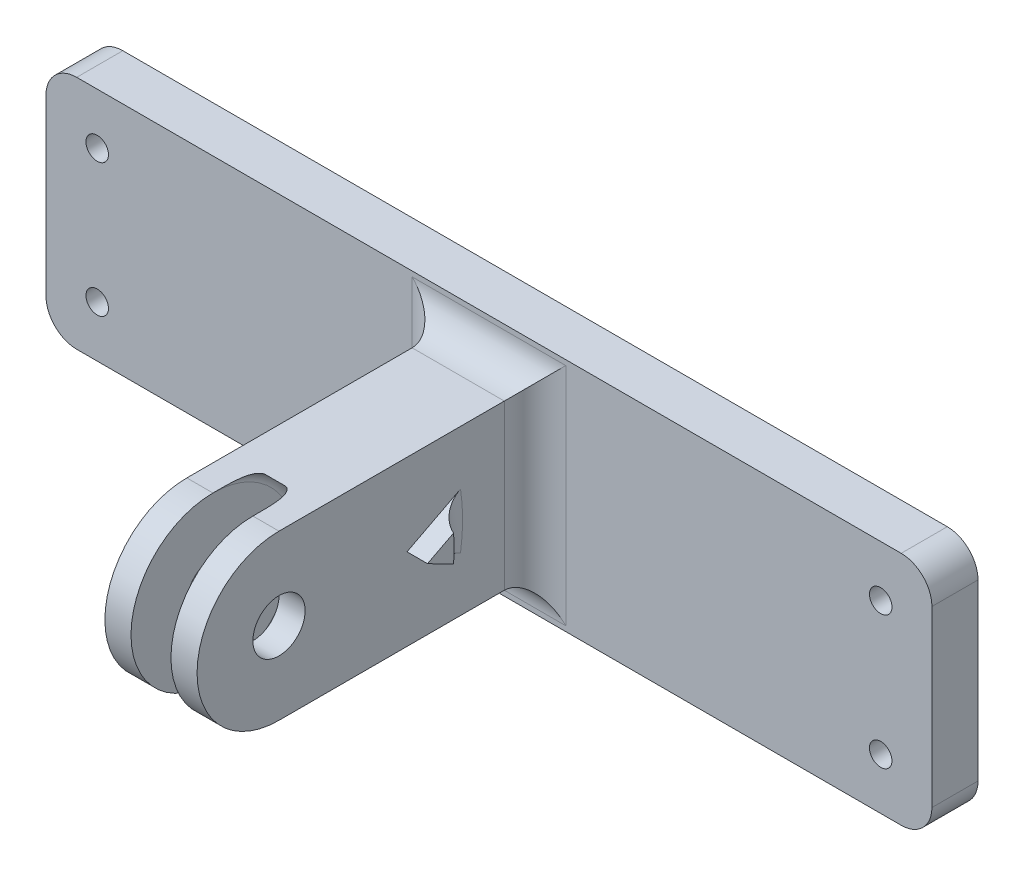
SolidWorks part; units mm, degrees
ref_plane "Front Plane" through (0, 0, 0) normal (0, 0, 1) x (1, 0, 0)
ref_plane "Top Plane" through (0, 0, 0) normal (0, 1, 0) x (1, 0, 0)
ref_plane "Right Plane" through (0, 0, 0) normal (1, 0, 0) x (0, 0, -1)
sketch "Sketch1" plane through (0, 0, 0) normal (0, 0, 1) x (1, 0, 0)
  line L1 (-38.25, 6.5) -> (38.25, 6.5) construction
  line L2 (-38.25, 6.5) -> (-38.25, -6.5) construction
  line L3 (-38.25, -6.5) -> (38.25, -6.5) construction
  line L4 (38.25, 6.5) -> (38.25, -6.5) construction
  line L5 (-38.25, 6.5) -> (38.25, -6.5) construction
  line L6 (-38.25, -6.5) -> (38.25, 6.5) construction
  line L7 (-43.25, 11.5) -> (43.25, 11.5)
  line L8 (-43.25, 11.5) -> (-43.25, -11.5)
  line L9 (-43.25, -11.5) -> (43.25, -11.5)
  line L10 (43.25, 11.5) -> (43.25, -11.5)
  line L11 (-43.25, 11.5) -> (43.25, -11.5) construction
  line L12 (-43.25, -11.5) -> (43.25, 11.5) construction
  circle A0 centre (38.25, 6.5) radius 1.1
  circle A1 centre (38.25, -6.5) radius 1.1
  circle A2 centre (-38.25, -6.5) radius 1.1
  circle A3 centre (-38.25, 6.5) radius 1.1
  point P0 (0, 0)
  point P6 (0, 0)
  dimension "D3" = 2.2
  dimension "D1" = 76.5
  dimension "D2" = 13
  dimension "D4" = 5
  dimension "D5" = 5
extrude "Boss-Extrude1" add sketch "Sketch1" along normal blind 4.5
sketch "Sketch2" plane through (0, 0, 0) normal (0, 0, -1) x (-1, 0, 0)
  line L0 (0, 11.5) -> (0, 0) construction
  line L1 (-43.25, 11.5) -> (43.25, 11.5) construction
  line L2 (0, 0) -> (43.25, 0) construction
  line L3 (43.25, 11.5) -> (43.25, -11.5) construction
  line L4 (-35.6042, 9.5) -> (35.6042, 9.5)
  line L5 (38.25, 2.5) -> (38.25, -2.5)
  line L6 (-38.25, 2.5) -> (-38.25, -2.5)
  line L7 (-35.6042, -9.5) -> (35.6042, -9.5)
  line L8 (5, 9.5) -> (5, -9.5)
  line L9 (-5, 9.5) -> (-5, -9.5)
  arc A0 (35.6042, 9.5) -> (38.25, 2.5) centre (38.25, 6.5) ccw
  arc A1 (-35.6042, 9.5) -> (-38.25, 2.5) centre (-38.25, 6.5) cw
  arc A2 (-35.6042, -9.5) -> (-38.25, -2.5) centre (-38.25, -6.5) ccw
  arc A3 (35.6042, -9.5) -> (38.25, -2.5) centre (38.25, -6.5) cw
  point P18 (38.25, 0)
  point P19 (0, 9.5)
  point P25 (0, -9.5)
  point P26 (-38.25, 0)
  dimension "D1" = 8
  dimension "D2" = 10
  dimension "D3" = 2
extrude "Cut-Extrude1" cut sketch "Sketch2" against normal blind 2 contours A2 L7 L9 L4 A1 L6 | L7 A3 L5 A0 L4 L8 region at (20.4394, 0, 0) region at (-20.4394, 0, 0)
sketch "Sketch3" plane through (0, 0, 0) normal (1, 0, 0) x (0, 0, -1)
  line L0 (0, 0) -> (-29.5, 0) construction
  line L1 (-29.5, 8) -> (-4.5, 8)
  line L2 (-4.5, -11.5) -> (-4.5, 11.5) construction
  line L3 (-4.5, 8) -> (-4.5, -8)
  line L4 (-29.5, -8) -> (-4.5, -8)
  arc A0 (-29.5, 8) -> (-29.5, -8) centre (-29.5, 0) ccw
  circle A1 centre (-29.5, 0) radius 2.55
  point P10 (-4.5, 0)
  dimension "D3" = 5.1
  dimension "D1" = 25
  dimension "D2" = 16
extrude "Boss-Extrude2" add sketch "Sketch3" along normal mid plane 9
sketch "Sketch6" plane through (0, 0, 0) normal (1, 0, 0) x (0, 0, -1)
  circle A0 centre (-29.5, 0) radius 9
  dimension "D1" = 18
extrude "Cut-Extrude3" cut sketch "Sketch6" against normal mid plane 3.9
fillet "Fillet1" radius 3 8 edges at (0, 8, 4.5) (0, -8, 4.5) (4.5, 0, 4.5) (-4.5, 0, 4.5) (43.25, -11.5, 2.25) (-43.25, 11.5, 2.25) (43.25, 11.5, 2.25) (-43.25, -11.5, 2.25)
fillet "Fillet2" radius 1 2 edges at (1.95, 0, 20.5) (-1.95, 0, 20.5)
fillet "Fillet3" radius 1 12 edges at (-38.25, -2.5, 1) (-38.25, 2.5, 1) (-35.6042, 9.5, 1) (-5, -9.5, 1) (-35.6042, -9.5, 1) (35.6042, -9.5, 1) (5, -9.5, 1) (5, 9.5, 1) (35.6042, 9.5, 1) (38.25, 2.5, 1) (38.25, -2.5, 1) (-5, 9.5, 1)
sketch "Sketch7" plane through (4.5, 0, 0) normal (1, 0, 0) x (0, 0, -1)
  line L0 (-29.5, 0) -> (-29.5, -15.1)
  line L1 (-29.5, 0) -> (-44.6, 0)
  line L2 (-29.5, 0) -> (-29.5, 15.1)
  line L3 (-29.5, 0) -> (-14.4, 0)
  line L4 (-29.5, 0) -> (-14.4575, -1.3161)
  line L5 (-29.5, 0) -> (-14.4575, 1.3161)
  line L6 (-14.4575, 1.3161) -> (-17, 0)
  line L7 (-17, 0) -> (-14.4575, -1.3161)
  line L8 (-14.4575, 1.3161) -> (-14.4575, -1.3161)
  circle A0 centre (-29.5, 0) radius 15.1
  point P10 (-29.5, 0)
  dimension "D1" = 30.2
  dimension "D3" = 5
  dimension "D4" = 5
  dimension "D5" = 12.5
  dimension "D2" = 4
extrude "Boss-Extrude3" add sketch "Sketch7" along normal blind 2 contours L8 L6 L3 | L8 L3 L7 | L3 A0 L8 | L8 A0 L3 region at (4.5, 0.4387, 15.305) region at (4.5, -0.4387, 15.305) region at (4.5, -0.4936, 14.4345) region at (4.5, 0.4936, 14.4345)
mirror "Mirror1" about plane through (0, 0, 0) normal (1, 0, 0) of "Boss-Extrude3"
fillet "Fillet4" radius 3 2 edges at (4.5, 0, 14.4) (-4.5, 0, 14.4)
